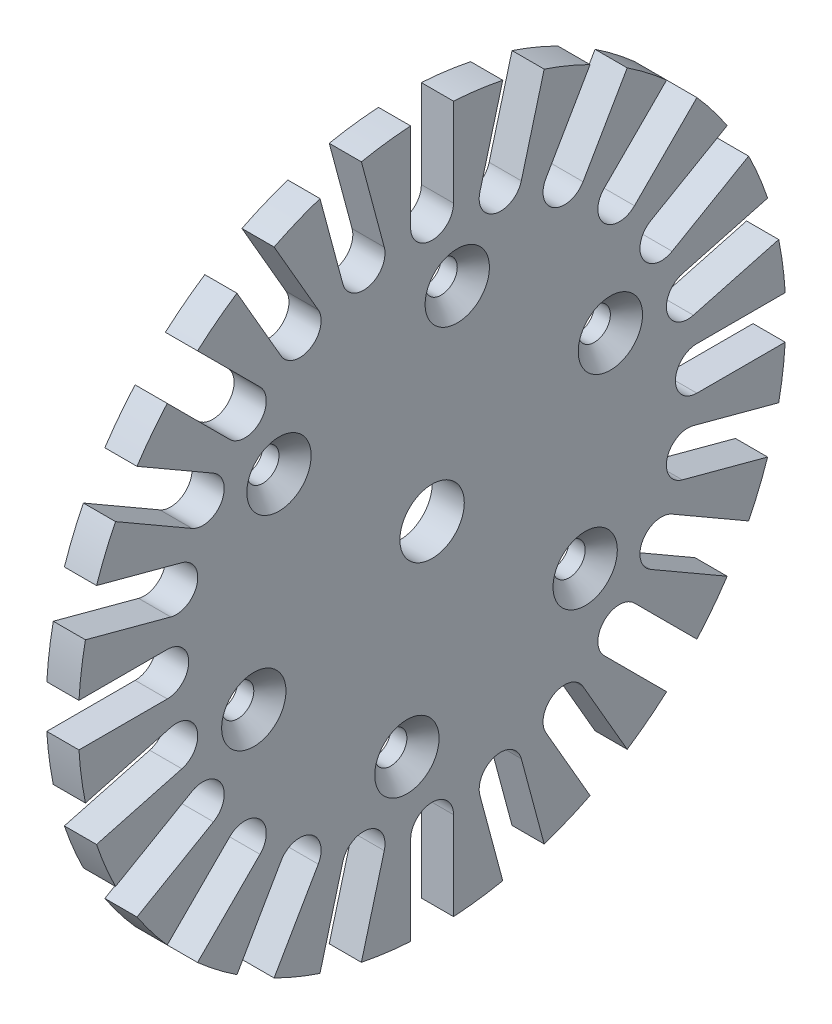
SolidWorks part; units mm, degrees
material "1060 Alloy"
ref_plane "Front Plane" through (0, 0, 0) normal (0, 0, 1) x (1, 0, 0)
ref_plane "Top Plane" through (0, 0, 0) normal (0, 1, 0) x (1, 0, 0)
ref_plane "Right Plane" through (0, 0, 0) normal (1, 0, 0) x (0, 0, -1)
sketch "Sketch1" plane through (0, 0, 0) normal (1, 0, 0) x (0, 0, -1)
  circle A0 centre (0, 0) radius 33
  dimension "D1" = 66
extrude "Boss-Extrude1" add sketch "Sketch1" along normal blind 3
sketch "Sketch3" plane through (3, 0, 0) normal (1, 0, 0) x (0, 0, -1)
  circle A0 centre (0, 0) radius 3.005
  dimension "D1" = 6.01
extrude "Cut-Extrude2" cut sketch "Sketch3" against normal up to next
sketch "Sketch4" plane through (3, 0, 0) normal (1, 0, 0) x (0, 0, -1)
  line L0 (-2, 33) -> (-2, 24.7)
  line L1 (2, 24.7) -> (2, 33)
  line L2 (2, 33) -> (-2, 33)
  arc A0 (-2, 24.7) -> (2, 24.7) centre (0, 24.7) ccw
  circle A1 centre (0, 0) radius 33 construction
  dimension "D1" = 4
  dimension "D2" = 8.3
extrude "Cut-Extrude3" cut sketch "Sketch4" against normal up to next
pattern_circular "CirPattern2" count 24 over 360 about axis through (3, 0, 0) along (1, 0, 0) of "Cut-Extrude3"
sketch "Sketch2" plane through (3, 0, 0) normal (1, 0, 0) x (0, 0, -1)
  line L0 (2.3495, 17.846) -> (0, 0) construction
  line L1 (0, 0) -> (3.005, 0) construction
  circle A0 centre (2.3495, 17.846) radius 1.5
  circle A1 centre (0, 0) radius 3.005 construction
  dimension "D1" = 3
  dimension "D2" = 18
  dimension "D3" = 82.5
extrude "Cut-Extrude1" cut sketch "Sketch2" against normal up to next
chamfer "Chamfer1" distance 1.5 angle 45 1 edges at (3, 17.846, -3.8495)
pattern_circular "CirPattern1" count 6 over 360 about axis through (3, 0, 0) along (1, 0, 0) of "Cut-Extrude1", "Chamfer1"
